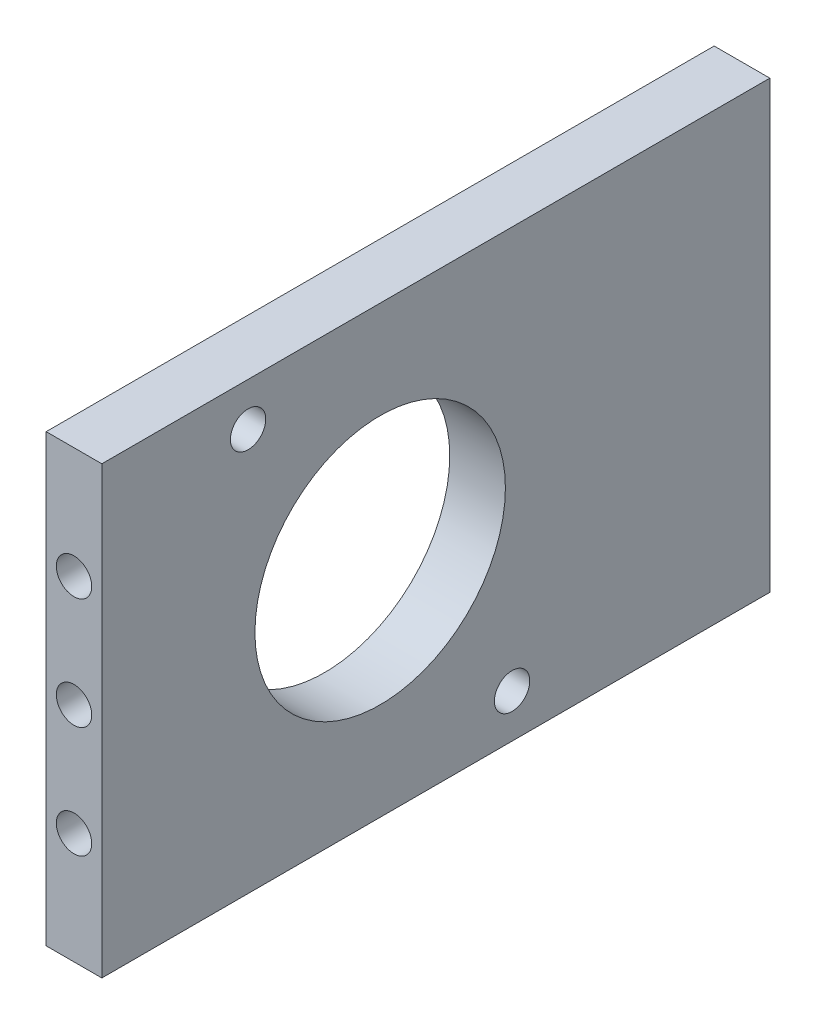
SolidWorks part; units mm, degrees
material "6061-T6 (SS)"
ref_plane "Front" through (0, 0, 0) normal (0, 0, 1) x (1, 0, 0)
ref_plane "Top" through (0, 0, 0) normal (0, 1, 0) x (1, 0, 0)
ref_plane "Right" through (0, 0, 0) normal (1, 0, 0) x (0, 0, -1)
sketch "Sketch2" plane through (0, 0, 0) normal (1, 0, 0) x (0, 0, -1)
  line L1 (-38.1, -25.4) -> (38.1, -25.4)
  line L2 (-38.1, -25.4) -> (-38.1, 25.4)
  line L3 (-38.1, 25.4) -> (38.1, 25.4)
  line L4 (38.1, -25.4) -> (38.1, 25.4)
  line L5 (-38.1, -25.4) -> (38.1, 25.4) construction
  line L6 (-38.1, 25.4) -> (38.1, -25.4) construction
  point P0 (0, 0)
  dimension "D1" = 76.2
  dimension "D2" = 50.8
extrude "Boss-Extrude2" add sketch "Sketch2" along normal blind 6.35
hole_wizard "#10-32 Tapped Hole1" positions "Sketch3" profile "Sketch5" tap size "#10-32" standard "ANSI Inch"
sketch "Sketch3" plane through (0, 0, 38.1) normal (0, 0, 1) x (1, 0, 0)
  line L0 (3.175, 25.4) -> (3.175, 12.7) construction
  line L1 (6.35, 25.4) -> (0, 25.4) construction
  line L3 (3.175, 12.7) -> (3.175, 0) construction
  line L4 (3.175, 0) -> (3.175, -12.7) construction
  line L5 (3.175, -12.7) -> (3.175, -25.4) construction
  line L6 (6.35, -25.4) -> (0, -25.4) construction
  point P0 (3.175, -12.7)
  point P2 (3.175, 0)
  point P6 (3.175, 12.7)
  point P48 (0, 0)
  point P49 (0, 0)
sketch "Sketch5" plane through (3.175, -12.7, 38.1) normal (1, 0, 0) x (0, -1, 0)
  line L0 (0, 0) -> (0, 13.2428)
  line L1 (0, 13.2428) -> (2.0193, 12.0294)
  line L2 (2.0193, 12.0294) -> (2.0193, 0)
  line L5 (2.0193, 0) -> (0, 0)
  line L10 (0, 13.2428) -> (-2.0193, 12.0294) construction
  line L11 (0, -6.35) -> (0, 107.95) construction
  dimension "Tap Drill Dia." = 4.0386
  dimension "Tap Drill Depth" = 12.0294
  dimension "Drill Angle" = 118
cosmetic thread "Hole Thread1" parameters "D1"=9.652, "D2"=4.826
cosmetic thread "Hole Thread3" parameters "D1"=9.652, "D2"=4.826
cosmetic thread "Hole Thread4" parameters "D1"=9.652, "D2"=4.826
sketch "Sketch6" plane through (6.35, 0, 0) normal (1, 0, 0) x (0, 0, -1)
  line L0 (-38.1, 25.4) -> (-38.1, -25.4) construction
  line L1 (-38.1, -25.4) -> (38.1, -25.4) construction
  circle A0 centre (-6.35, 0) radius 14.2875
  dimension "D1" = 31.75
  dimension "D3" = 28.575
  dimension "D2" = 25.4
extrude "Cut-Extrude1" cut sketch "Sketch6" against normal through all
sketch "Sketch10" plane through (0, 0, 0) normal (-1, 0, 0) x (0, 0, 1)
  point P3 (-8.6978, -20.4449)
  point P8 (21.4195, 20.4646)
hole_wizard "#10-32 Tapped Hole2" positions "Sketch10" profile "Sketch9" tap size "#10-32" standard "ANSI Inch"
sketch "Sketch9" plane through (0, -20.4449, -8.6978) normal (0, 1, 0) x (0, 0, 1)
  line L0 (0, 0) -> (0, 13.2428)
  line L1 (0, 13.2428) -> (2.0193, 12.0294)
  line L2 (2.0193, 12.0294) -> (2.0193, 0)
  line L5 (2.0193, 0) -> (0, 0)
  line L10 (0, 13.2428) -> (-2.0193, 12.0294) construction
  line L11 (0, -6.35) -> (0, 107.95) construction
  dimension "Tap Drill Dia." = 4.0386
  dimension "Tap Drill Depth" = 12.0294
  dimension "Drill Angle" = 118
cosmetic thread "Hole Thread5" parameters "D1"=9.652, "D2"=4.826
cosmetic thread "Hole Thread6" parameters "D1"=9.652, "D2"=4.826
